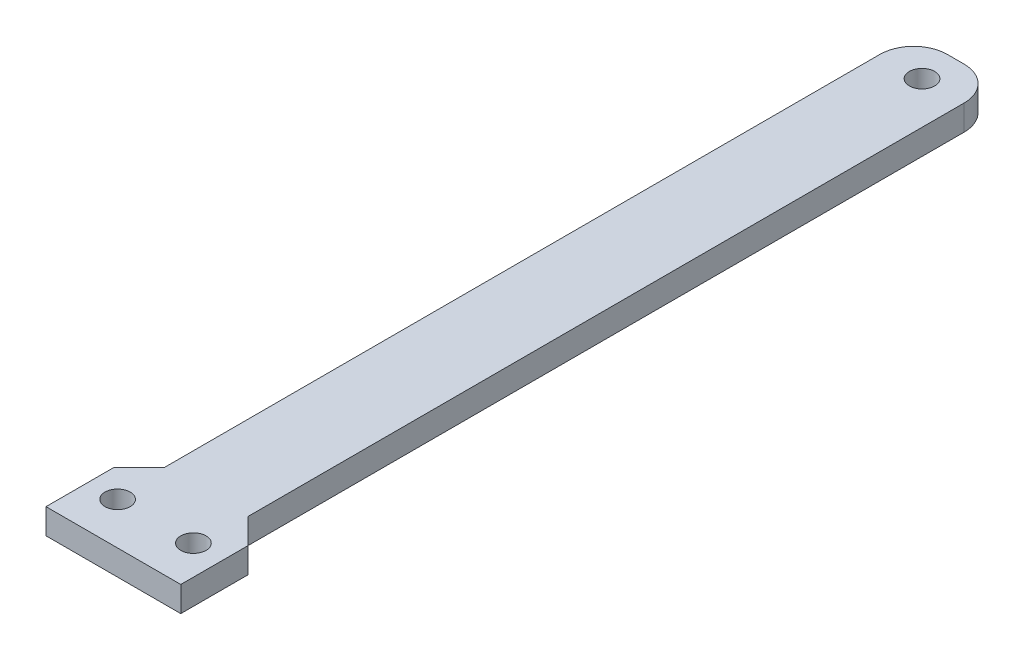
SolidWorks part; units mm, degrees
material "普通碳钢"
ref_plane "前视基准面" through (0, 0, 0) normal (0, 0, 1) x (1, 0, 0)
ref_plane "上视基准面" through (0, 0, 0) normal (0, 1, 0) x (1, 0, 0)
ref_plane "右视基准面" through (0, 0, 0) normal (1, 0, 0) x (0, 0, -1)
sketch "草图1" plane through (0, 0, 0) normal (0, 1, 0) x (1, 0, 0)
  line L0 (0, 0) -> (0, -50) construction
  line L2 (-5, -46) -> (-5, 46)
  line L3 (-5, 46) -> (5, 46)
  line L4 (5, -46) -> (5, 46)
  line L5 (-5, -46) -> (5, 46) construction
  line L6 (-5, 46) -> (5, -46) construction
  line L7 (5, -46) -> (8, -46)
  line L8 (-8, -54) -> (8, -54)
  line L9 (-8, -54) -> (-8, -46)
  line L10 (-8, -46) -> (-5, -46)
  line L11 (8, -54) -> (8, -46)
  line L12 (-8, -54) -> (8, -46) construction
  line L13 (-8, -46) -> (8, -54) construction
  point P0 (0, 0)
  dimension "D1" = 10
  dimension "D2" = 8
  dimension "D3" = 100
  dimension "D4" = 3
extrude "凸台-拉伸1" add sketch "草图1" along normal blind 3
hole_wizard "M3 间隙孔1" positions "草图3" profile "草图2" hole size "M3" standard "GB" end condition through all
sketch "草图3" plane through (0, 3, 0) normal (0, 1, 0) x (1, 0, 0)
  line L2 (0, 0) -> (0, -54) construction
  line L4 (-8, -54) -> (8, -54) construction
  line L5 (5, 46) -> (-5, 46) construction
  point P2 (4.5, -49)
  point P7 (0, 42)
  point P22 (-4.5, -49)
  dimension "D1" = 9
  dimension "D2" = 5
  dimension "D3" = 4
sketch "草图2" plane through (4.5, 3, 49) normal (1, 0, 0) x (0, 0, 1)
  line L0 (0, 0) -> (0, 3)
  line L1 (0, 3) -> (1.5, 3)
  line L2 (1.5, 3) -> (1.5, 0)
  line L5 (1.5, 0) -> (0, 0)
  line L11 (0, -6.35) -> (0, 107.95) construction
  dimension "通孔孔直径" = 3
  dimension "通孔孔深度" = 3
ref_point "点1"
chamfer "倒角2" distance 3 angle 45 2 edges at (5, 1.5, 46) (-5, 1.5, 46)
fillet "圆角1" radius 4 2 edges at (5, 1.5, -46) (-5, 1.5, -46)
move or copy body "实体-移动/复制1" [suppressed] bodies to move or copy 107
